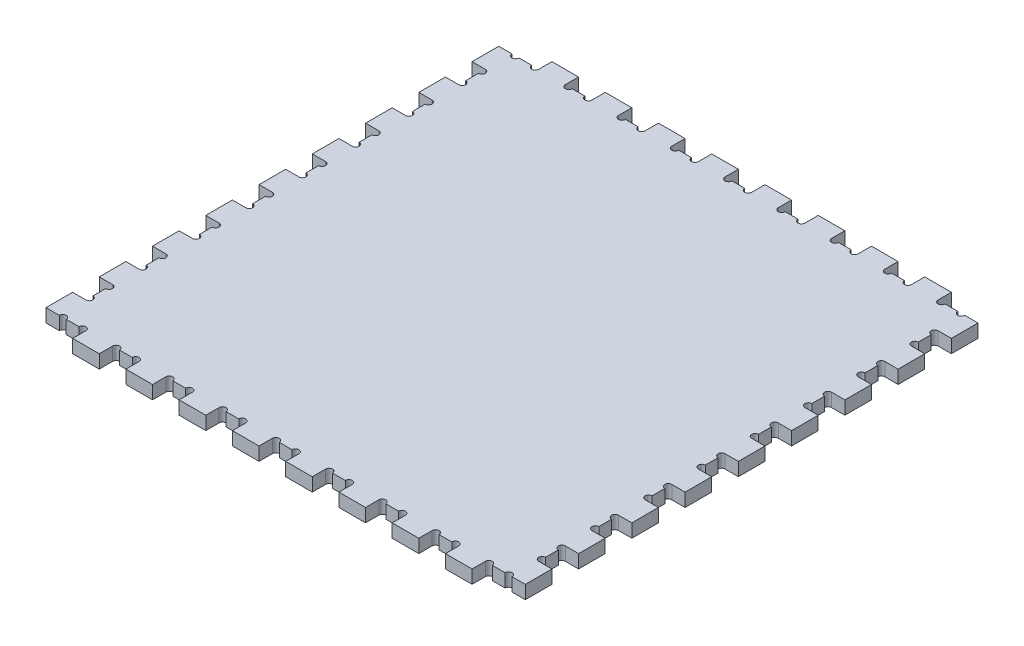
SolidWorks part; units mm, degrees
ref_plane "Front Plane" through (0, 0, 0) normal (0, 0, 1) x (1, 0, 0)
ref_plane "Top Plane" through (0, 0, 0) normal (0, 1, 0) x (1, 0, 0)
ref_plane "Right Plane" through (0, 0, 0) normal (1, 0, 0) x (0, 0, -1)
sketch "Sketch1" plane through (0, 0, 0) normal (0, 1, 0) x (1, 0, 0)
  line L1 (228.6, -228.6) -> (-228.6, -228.6)
  line L2 (228.6, -228.6) -> (228.6, 228.6)
  line L3 (228.6, 228.6) -> (-228.6, 228.6)
  line L4 (-228.6, -228.6) -> (-228.6, 228.6)
  line L5 (228.6, -228.6) -> (-228.6, 228.6) construction
  line L6 (228.6, 228.6) -> (-228.6, -228.6) construction
  point P0 (0, 0)
  dimension "D1" = 457.2
  dimension "D2" = 457.2
extrude "Boss-Extrude1" add sketch "Sketch1" along normal blind 12.7
sketch "Sketch2" plane through (0, 12.7, 0) normal (0, 1, 0) x (1, 0, 0)
  line L0 (228.6, 228.6) -> (-228.6, 228.6) construction
  line L1 (-215.9, 228.6) -> (-190.5, 228.6)
  line L2 (-215.9, 228.6) -> (-215.9, 215.9)
  line L3 (-215.9, 215.9) -> (-190.5, 215.9)
  line L4 (-190.5, 228.6) -> (-190.5, 215.9)
  line L5 (-215.9, 215.9) -> (-228.6, 215.9) construction
  line L6 (-228.6, 228.6) -> (-228.6, -228.6) construction
  circle A0 centre (-212.598, 215.9) radius 3.302
  circle A1 centre (-193.802, 215.9) radius 3.302
  line M8 (228.6, 228.6) -> (-228.6, 228.6)
  dimension "D3" = 6.604
  dimension "D4" = 6.604
  dimension "D1" = 25.4
  dimension "D2" = 12.7
  dimension "D5" = 12.7
extrude "Cut-Extrude1" cut sketch "Sketch2" against normal blind 12.7 contours A1 L4 L2 A0 L3 M8 | L3 A0 | L3 A1 | L3 A1 | L3 A0 region at (-203.2, 12.7, -222.8379) region at (-212.598, 12.7, -217.3014) region at (-212.598, 12.7, -214.4986) region at (-193.802, 12.7, -214.4986) region at (-193.802, 12.7, -217.3014)
pattern_linear "LPattern1" count 9 spacing 50.8 along (1, 0, 0) of "Cut-Extrude1"
ref_plane "Plane1" through (0, 0, 0) normal (0, 0, -1) x (-1, 0, 0)
ref_plane "Plane2" through (0, 0, 0) normal (-1, 0, 0) x (0, 0, 1)
mirror "Mirror1" about plane through (0, 0, 0) normal (0, 0, -1) of "LPattern1"
sketch "Sketch3" plane through (0, 12.7, 0) normal (0, 1, 0) x (1, 0, 0)
  line L1 (-228.6, 228.6) -> (-215.9, 228.6)
  line L2 (-228.6, 228.6) -> (-228.6, 215.9)
  line L3 (-228.6, 215.9) -> (-215.9, 215.9)
  line L4 (-215.9, 228.6) -> (-215.9, 215.9)
extrude "Cut-Extrude2" cut sketch "Sketch3" against normal through all
mirror "Mirror2" about plane through (0, 0, 0) normal (-1, 0, 0) of "Cut-Extrude2"
mirror "Mirror3" about plane through (0, 0, 0) normal (0, 0, -1) of "Mirror2"
sketch "Sketch4" plane through (0, 12.7, 0) normal (0, 1, 0) x (1, 0, 0)
  line L0 (-228.6, 215.9) -> (-228.6, -215.9) construction
  line L1 (-228.6, 190.5) -> (-215.9, 190.5)
  line L2 (-228.6, 190.5) -> (-228.6, 165.1)
  line L3 (-228.6, 165.1) -> (-215.9, 165.1)
  line L4 (-215.9, 190.5) -> (-215.9, 165.1)
  line L5 (-215.9, 190.5) -> (-186.3664, 190.5) construction
  line L6 (-186.3664, 190.5) -> (-186.3664, 228.6) construction
  line L7 (-165.1, 228.6) -> (-190.5, 228.6) construction
  circle A0 centre (-215.9, 187.198) radius 3.302
  circle A1 centre (-215.9, 168.402) radius 3.302
  dimension "D3" = 6.604
  dimension "D4" = 6.604
  dimension "D1" = 12.7
  dimension "D2" = 25.4
  dimension "D5" = 38.1
extrude "Cut-Extrude3" cut sketch "Sketch4" against normal through all contours A1 L4 A0 L1 L2 L3 | L4 A0 | L4 A1 | L4 A1 | L4 A0 region at (-222.8379, 12.7, -177.8) region at (-214.4986, 12.7, -187.198) region at (-217.3014, 12.7, -187.198) region at (-217.3014, 12.7, -168.402) region at (-214.4986, 12.7, -168.402)
pattern_linear "LPattern2" count 9 spacing 50.8 along (0, 0, 1) of "Cut-Extrude3"
mirror "Mirror4" about plane through (0, 0, 0) normal (-1, 0, 0) of "LPattern2"
